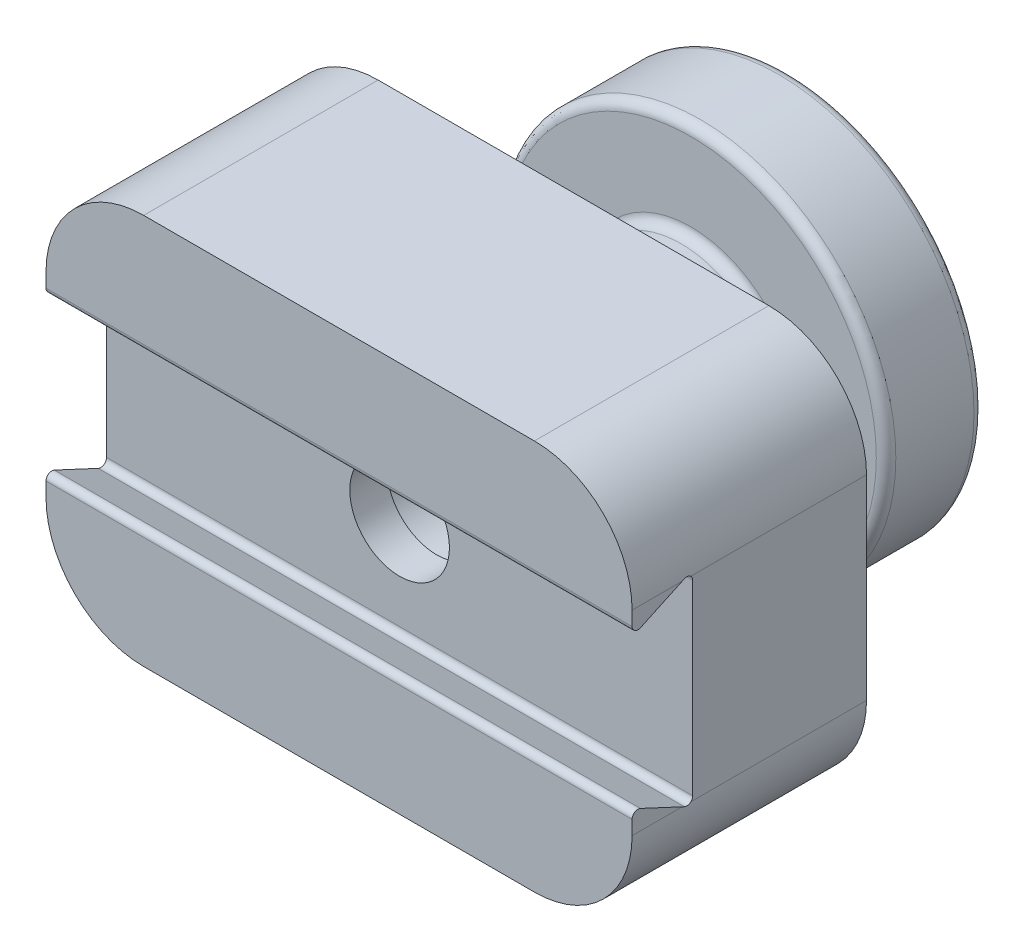
SolidWorks part; units mm, degrees
ref_plane "Front" through (0, 0, 0) normal (0, 0, 1) x (1, 0, 0)
ref_plane "Top" through (0, 0, 0) normal (0, 1, 0) x (1, 0, 0)
ref_plane "Right" through (0, 0, 0) normal (1, 0, 0) x (0, 0, -1)
sketch "Sketch1" plane through (0, 0, 0) normal (0, 0, 1) x (1, 0, 0)
  line L0 (18.3647, 0) -> (-19.4746, 0) construction
  arc A1 (10, 0) -> (-10, 0) centre (0, 0) ccw
  arc A2 (10, 0) -> (-10, 0) centre (0, 0) cw
  point P4 (0, -2.5)
  dimension "D2" = 10
extrude "Boss-Extrude1" add sketch "Sketch1" along normal blind 5
sketch "Sketch2" plane through (0, 0, 0) normal (0, 0, 1) x (1, 0, 0)
  circle A0 centre (0, 0) radius 5
  dimension "D1" = 10
extrude "Boss-Extrude2" add sketch "Sketch2" along normal blind 11
ref_plane "Plane1" through (0, 0, 11) normal (0, 0, 1) x (1, 0, 0)
ref_point "Point1"
sketch "Sketch3" plane through (0, 0, 11) normal (0, 0, 1) x (1, 0, 0)
  line L1 (-15, 10) -> (15, 10)
  line L2 (-15, 10) -> (-15, -10)
  line L3 (-15, -10) -> (15, -10)
  line L4 (15, 10) -> (15, -10)
  line L5 (-15, 10) -> (15, -10) construction
  line L6 (-15, -10) -> (15, 10) construction
  point P0 (0, 0)
  dimension "D1" = 20
  dimension "D2" = 30
  dimension "D6" = 30
extrude "Boss-Extrude3" add sketch "Sketch3" along normal blind 12
ref_plane "Plane2" through (-10, 0, 0) normal (1, 0, 0) x (0, 0, -1)
sketch "Sketch5" plane through (-10, 0, 0) normal (1, 0, 0) x (0, 0, -1)
  line L0 (-23, 3.8044) -> (-19.9, 5.25)
  line L2 (-19.9, 5.25) -> (-19.9, -5.25)
  line L3 (-19.9, -5.25) -> (-23, -3.8044)
  line L4 (-23, -3.8044) -> (-23, 3.8044)
  line L5 (-23, 0) -> (-19.9, 0) construction
  line L7 (-23, 10) -> (-23, -10) construction
  line L8 (-23, 10) -> (-11, 10) construction
  line L9 (-23, -10) -> (-23, 10) construction
  dimension "D1" = 10.5
  dimension "D2" = 10
  dimension "D3" = 3.1
  dimension "D4" = 5.25
  dimension "D5" = 3.1
  dimension "D6" = 3.8044
  dimension "D8" = 65
extrude "Cut-Extrude1" cut sketch "Sketch5" along normal through all both and the other way through all
sketch "Sketch6" plane through (0, 0, 23) normal (0, 0, 1) x (1, 0, 0)
  circle A0 centre (0, 0) radius 2.55
  point P2 (0, 0)
  dimension "D1" = 5.1
extrude "Cut-Extrude2" cut sketch "Sketch6" against normal blind 5
pattern_linear "LPattern1" [suppressed] count 3 spacing 7 of bodies 105
fillet "Fillet1" radius 0.3 4 edges at (0, -5.25, 19.9) (0, -3.8044, 23) (0, 5.25, 19.9) (0, 3.8044, 23)
fillet "Fillet2" radius 5 4 edges at (-15, -10, 17) (15, -10, 17) (15, 10, 17) (-15, 10, 17)
fillet "Fillet3" radius 0.5 4 edges at (10, 0, 0) (-10, 0, 5) (-5, 0, 5) (5, 0, 11)
sketch "Sketch7" plane through (0, 0, 18) normal (0, 0, 1) x (1, 0, 0)
  circle A0 centre (0, 0) radius 2.9
  dimension "D1" = 5.8
extrude "Cut-Extrude3" cut sketch "Sketch7" against normal blind 6
